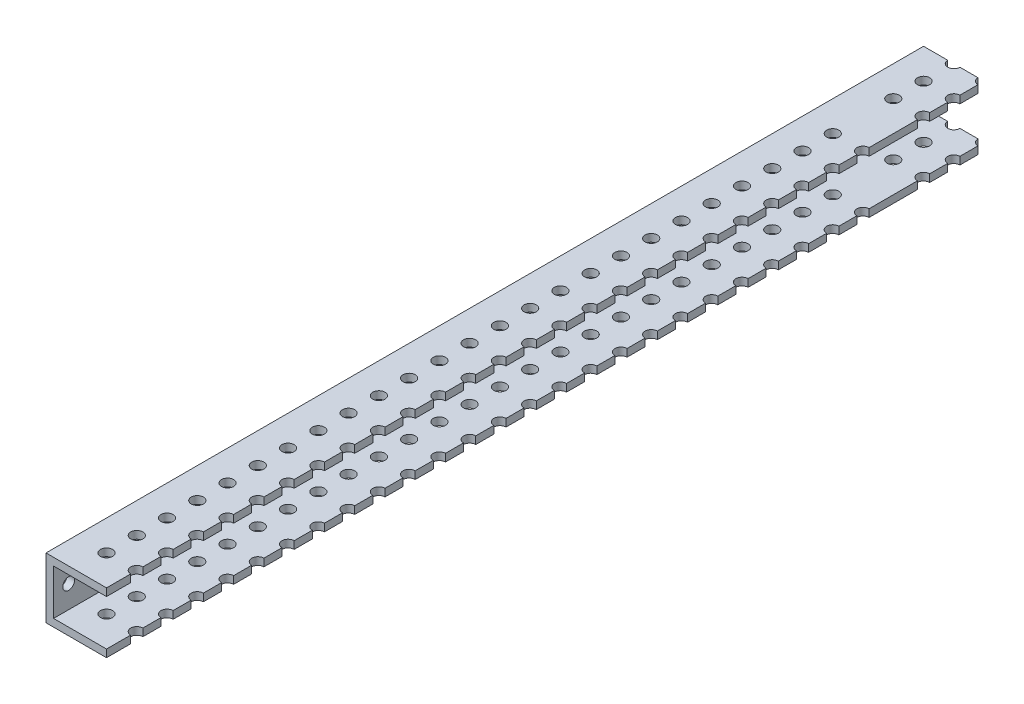
SolidWorks part; units mm, degrees
material "6061-T6 (SS)"
ref_plane "Front Plane" through (0, 0, 0) normal (0, 0, 1) x (1, 0, 0)
ref_plane "Top Plane" through (0, 0, 0) normal (0, 1, 0) x (1, 0, 0)
ref_plane "Right Plane" through (0, 0, 0) normal (1, 0, 0) x (0, 0, -1)
sketch "Sketch1" plane through (0, 0, 0) normal (0, 0, 1) x (1, 0, 0)
  line L0 (-22.225, 9.525) -> (22.225, 9.525)
  line L1 (-25.4, 12.7) -> (25.4, 12.7)
  line L2 (-25.4, 12.7) -> (-25.4, -12.7)
  line L3 (-25.4, -12.7) -> (25.4, -12.7)
  line L4 (25.4, 12.7) -> (25.4, -12.7)
  line L5 (22.225, 9.525) -> (22.225, -9.525)
  line L6 (-22.225, -9.525) -> (22.225, -9.525)
  line L7 (-22.225, 9.525) -> (-22.225, -9.525)
  line L8 (-25.4, 12.7) -> (25.4, -12.7) construction
  line L9 (25.4, 12.7) -> (-25.4, -12.7) construction
  point P5 (0, 0)
  dimension "D1" = 50.8
  dimension "D2" = 25.4
  dimension "D3" = 3.175
extrude "Boss-Extrude1" add sketch "Sketch1" along normal mid plane 368.3
sketch "Sketch2" plane through (0, 12.7, 0) normal (0, 1, 0) x (1, 0, 0)
  line L0 (25.4, -184.15) -> (-25.4, -184.15) construction
  line L1 (-25.4, -184.15) -> (-25.4, 184.15) construction
  line L2 (-12.7, -171.45) -> (0, -171.45) construction
  line L3 (0, -171.45) -> (12.7, -171.45) construction
  line L4 (25.4, 184.15) -> (-25.4, 184.15) construction
  circle A0 centre (0, -171.45) radius 2.5527
  circle A1 centre (12.7, -171.45) radius 2.5527
  circle A2 centre (-12.7, -171.45) radius 2.5527
  circle A3 centre (-12.7, -158.75) radius 2.5527
  circle A4 centre (0, -158.75) radius 2.5527
  circle A5 centre (12.7, -158.75) radius 2.5527
  circle A6 centre (-12.7, -146.05) radius 2.5527
  circle A7 centre (0, -146.05) radius 2.5527
  circle A8 centre (12.7, -146.05) radius 2.5527
  circle A9 centre (-12.7, -133.35) radius 2.5527
  circle A10 centre (0, -133.35) radius 2.5527
  circle A11 centre (12.7, -133.35) radius 2.5527
  circle A12 centre (-12.7, -120.65) radius 2.5527
  circle A13 centre (0, -120.65) radius 2.5527
  circle A14 centre (12.7, -120.65) radius 2.5527
  circle A15 centre (-12.7, -107.95) radius 2.5527
  circle A16 centre (0, -107.95) radius 2.5527
  circle A17 centre (12.7, -107.95) radius 2.5527
  circle A18 centre (-12.7, -95.25) radius 2.5527
  circle A19 centre (0, -95.25) radius 2.5527
  circle A20 centre (12.7, -95.25) radius 2.5527
  circle A21 centre (-12.7, -82.55) radius 2.5527
  circle A22 centre (0, -82.55) radius 2.5527
  circle A23 centre (12.7, -82.55) radius 2.5527
  circle A24 centre (-12.7, -69.85) radius 2.5527
  circle A25 centre (0, -69.85) radius 2.5527
  circle A26 centre (12.7, -69.85) radius 2.5527
  circle A27 centre (-12.7, -57.15) radius 2.5527
  circle A28 centre (0, -57.15) radius 2.5527
  circle A29 centre (12.7, -57.15) radius 2.5527
  circle A30 centre (-12.7, -44.45) radius 2.5527
  circle A31 centre (0, -44.45) radius 2.5527
  circle A32 centre (12.7, -44.45) radius 2.5527
  circle A33 centre (-12.7, -31.75) radius 2.5527
  circle A34 centre (0, -31.75) radius 2.5527
  circle A35 centre (12.7, -31.75) radius 2.5527
  circle A36 centre (-12.7, -19.05) radius 2.5527
  circle A37 centre (0, -19.05) radius 2.5527
  circle A38 centre (12.7, -19.05) radius 2.5527
  circle A39 centre (-12.7, -6.35) radius 2.5527
  circle A40 centre (0, -6.35) radius 2.5527
  circle A41 centre (12.7, -6.35) radius 2.5527
  circle A42 centre (-12.7, 6.35) radius 2.5527
  circle A43 centre (0, 6.35) radius 2.5527
  circle A44 centre (12.7, 6.35) radius 2.5527
  circle A45 centre (-12.7, 19.05) radius 2.5527
  circle A46 centre (0, 19.05) radius 2.5527
  circle A47 centre (12.7, 19.05) radius 2.5527
  circle A48 centre (-12.7, 31.75) radius 2.5527
  circle A49 centre (0, 31.75) radius 2.5527
  circle A50 centre (12.7, 31.75) radius 2.5527
  circle A51 centre (-12.7, 44.45) radius 2.5527
  circle A52 centre (0, 44.45) radius 2.5527
  circle A53 centre (12.7, 44.45) radius 2.5527
  circle A54 centre (-12.7, 57.15) radius 2.5527
  circle A55 centre (0, 57.15) radius 2.5527
  circle A56 centre (12.7, 57.15) radius 2.5527
  circle A57 centre (-12.7, 69.85) radius 2.5527
  circle A58 centre (0, 69.85) radius 2.5527
  circle A59 centre (12.7, 69.85) radius 2.5527
  circle A60 centre (-12.7, 82.55) radius 2.5527
  circle A61 centre (0, 82.55) radius 2.5527
  circle A62 centre (12.7, 82.55) radius 2.5527
  circle A63 centre (-12.7, 95.25) radius 2.5527
  circle A64 centre (0, 95.25) radius 2.5527
  circle A65 centre (12.7, 95.25) radius 2.5527
  circle A66 centre (-12.7, 107.95) radius 2.5527
  circle A67 centre (0, 107.95) radius 2.5527
  circle A68 centre (12.7, 107.95) radius 2.5527
  circle A69 centre (-12.7, 120.65) radius 2.5527
  circle A70 centre (0, 120.65) radius 2.5527
  circle A71 centre (12.7, 120.65) radius 2.5527
  circle A72 centre (-12.7, 133.35) radius 2.5527
  circle A73 centre (0, 133.35) radius 2.5527
  circle A74 centre (12.7, 133.35) radius 2.5527
  circle A75 centre (-12.7, 146.05) radius 2.5527 construction
  circle A76 centre (0, 146.05) radius 2.5527 construction
  circle A77 centre (12.7, 146.05) radius 2.5527 construction
  circle A78 centre (-12.7, 158.75) radius 2.5527
  circle A79 centre (0, 158.75) radius 2.5527
  circle A80 centre (12.7, 158.75) radius 2.5527
  circle A81 centre (-12.7, 171.45) radius 2.5527
  circle A82 centre (0, 171.45) radius 2.5527
  circle A83 centre (12.7, 171.45) radius 2.5527
  circle A84 centre (-12.7, 184.15) radius 2.5527
  circle A85 centre (0, 184.15) radius 2.5527
  circle A86 centre (12.7, 184.15) radius 2.5527
  circle A87 centre (-12.7, 196.85) radius 2.5527
  circle A88 centre (0, 196.85) radius 2.5527
  circle A89 centre (12.7, 196.85) radius 2.5527
  circle A90 centre (-12.7, 209.55) radius 2.5527
  circle A91 centre (0, 209.55) radius 2.5527
  circle A92 centre (12.7, 209.55) radius 2.5527
  circle A93 centre (-12.7, 222.25) radius 2.5527
  circle A94 centre (0, 222.25) radius 2.5527
  circle A95 centre (12.7, 222.25) radius 2.5527
  circle A96 centre (-12.7, 234.95) radius 2.5527
  circle A97 centre (0, 234.95) radius 2.5527
  circle A98 centre (12.7, 234.95) radius 2.5527
  circle A99 centre (-12.7, 247.65) radius 2.5527
  circle A100 centre (0, 247.65) radius 2.5527
  circle A101 centre (12.7, 247.65) radius 2.5527
  circle A108 centre (-12.7, 273.05) radius 2.5527 [skipped]
  circle A109 centre (0, 273.05) radius 2.5527 [skipped]
  circle A110 centre (12.7, 273.05) radius 2.5527 [skipped]
  circle A111 centre (-12.7, 260.35) radius 2.5527 [skipped]
  circle A112 centre (0, 260.35) radius 2.5527 [skipped]
  circle A113 centre (12.7, 260.35) radius 2.5527 [skipped]
  circle A114 centre (12.7, 260.35) radius 2.5527
  circle A115 centre (0, 260.35) radius 2.5527
  circle A116 centre (-12.7, 260.35) radius 2.5527
  circle A117 centre (12.7, 273.05) radius 2.5527
  circle A118 centre (0, 273.05) radius 2.5527
  circle A119 centre (-12.7, 273.05) radius 2.5527
  circle A120 centre (12.7, 285.75) radius 2.5527
  circle A121 centre (0, 285.75) radius 2.5527
  circle A122 centre (-12.7, 285.75) radius 2.5527
  circle A123 centre (12.7, 298.45) radius 2.5527
  circle A124 centre (0, 298.45) radius 2.5527
  circle A125 centre (-12.7, 298.45) radius 2.5527
  circle A126 centre (12.7, 311.15) radius 2.5527
  circle A127 centre (0, 311.15) radius 2.5527
  circle A128 centre (-12.7, 311.15) radius 2.5527
  circle A129 centre (12.7, 323.85) radius 2.5527
  circle A130 centre (0, 323.85) radius 2.5527
  circle A131 centre (-12.7, 323.85) radius 2.5527
  circle A132 centre (12.7, 336.55) radius 2.5527
  circle A133 centre (0, 336.55) radius 2.5527
  circle A134 centre (-12.7, 336.55) radius 2.5527
  circle A135 centre (12.7, 349.25) radius 2.5527
  circle A136 centre (0, 349.25) radius 2.5527
  circle A137 centre (-12.7, 349.25) radius 2.5527
  circle A138 centre (12.7, 361.95) radius 2.5527
  circle A139 centre (0, 361.95) radius 2.5527
  circle A140 centre (-12.7, 361.95) radius 2.5527
  circle A141 centre (12.7, 374.65) radius 2.5527
  circle A142 centre (0, 374.65) radius 2.5527
  circle A143 centre (-12.7, 374.65) radius 2.5527
  circle A144 centre (12.7, 387.35) radius 2.5527
  circle A145 centre (0, 387.35) radius 2.5527
  circle A146 centre (-12.7, 387.35) radius 2.5527
  circle A147 centre (12.7, 400.05) radius 2.5527
  circle A148 centre (0, 400.05) radius 2.5527
  circle A149 centre (-12.7, 400.05) radius 2.5527
  circle A150 centre (12.7, 412.75) radius 2.5527
  circle A151 centre (0, 412.75) radius 2.5527
  circle A152 centre (-12.7, 412.75) radius 2.5527
  dimension "D2" = 5.1054
  dimension "D4" = 12.7
  dimension "D1" = 12.7
  dimension "D3" = 25.4
  dimension "D6" = 12.7
  dimension "D7" = 63.5
  dimension "D5" = 36
  dimension "D8" = 14
extrude "Cut-Extrude1" cut sketch "Sketch2" against normal through all
sketch "Sketch4" plane through (25.4, 0, 0) normal (1, 0, 0) x (0, 0, -1)
  line L1 (-184.15, -12.7) -> (-184.15, 12.7) construction
  line L2 (-184.15, -12.7) -> (184.15, -12.7) construction
  circle A2 centre (-177.8, 0) radius 2.4892
  circle A3 centre (-165.1, 0) radius 2.4892
  circle A16 centre (-152.4, 0) radius 2.4892
  circle A17 centre (-139.7, 0) radius 2.4892
  circle A18 centre (-127, 0) radius 2.4892
  circle A19 centre (254, 0) radius 2.4892
  circle A20 centre (266.7, 0) radius 2.4892
  circle A21 centre (279.4, 0) radius 2.4892
  circle A22 centre (292.1, 0) radius 2.4892
  circle A23 centre (304.8, 0) radius 2.4892
  circle A24 centre (317.5, 0) radius 2.4892
  circle A25 centre (330.2, 0) radius 2.4892
  circle A26 centre (342.9, 0) radius 2.4892
  circle A27 centre (355.6, 0) radius 2.4892
  circle A28 centre (368.3, 0) radius 2.4892
  circle A29 centre (381, 0) radius 2.4892
  circle A30 centre (393.7, 0) radius 2.4892
  circle A31 centre (406.4, 0) radius 2.4892
  circle A32 centre (419.1, 0) radius 2.4892
  circle A35 centre (-114.3, 0) radius 2.4892
  circle A36 centre (-101.6, 0) radius 2.4892
  circle A37 centre (-88.9, 0) radius 2.4892
  circle A38 centre (-76.2, 0) radius 2.4892
  circle A39 centre (-63.5, 0) radius 2.4892
  circle A40 centre (-50.8, 0) radius 2.4892
  circle A41 centre (-38.1, 0) radius 2.4892
  circle A42 centre (-25.4, 0) radius 2.4892
  circle A43 centre (-12.7, 0) radius 2.4892
  circle A44 centre (0, 0) radius 2.4892
  circle A45 centre (12.7, 0) radius 2.4892
  circle A46 centre (25.4, 0) radius 2.4892
  circle A47 centre (38.1, 0) radius 2.4892
  circle A48 centre (50.8, 0) radius 2.4892
  circle A49 centre (63.5, 0) radius 2.4892
  circle A50 centre (76.2, 0) radius 2.4892
  circle A51 centre (88.9, 0) radius 2.4892
  circle A52 centre (101.6, 0) radius 2.4892
  circle A53 centre (114.3, 0) radius 2.4892
  circle A54 centre (127, 0) radius 2.4892
  circle A55 centre (139.7, 0) radius 2.4892
  circle A56 centre (152.4, 0) radius 2.4892
  circle A57 centre (165.1, 0) radius 2.4892
  circle A58 centre (177.8, 0) radius 2.4892
  circle A59 centre (190.5, 0) radius 2.4892
  circle A60 centre (203.2, 0) radius 2.4892
  circle A61 centre (215.9, 0) radius 2.4892
  circle A62 centre (228.6, 0) radius 2.4892
  circle A63 centre (241.3, 0) radius 2.4892
  dimension "D2" = 4.9784
  dimension "D1" = 6.35
  dimension "D3" = 12.7
  dimension "D4" = 12.7
  dimension "D5" = 34
  dimension "D6" = 10
  dimension "D7" = 6
extrude "Cut-Extrude3" cut sketch "Sketch4" against normal through all
sketch "Sketch6" plane through (0, 12.7, 0) normal (0, 1, 0) x (1, 0, 0)
  line L0 (0, -184.15) -> (0, 184.15)
  line L1 (25.4, -184.15) -> (-25.4, -184.15) construction
  line L2 (0, 184.15) -> (25.4, 184.15)
  line L3 (25.4, 184.15) -> (25.4, -184.15)
  line L4 (25.4, -184.15) -> (0, -184.15)
extrude "Cut-Extrude5" cut sketch "Sketch6" against normal through all
